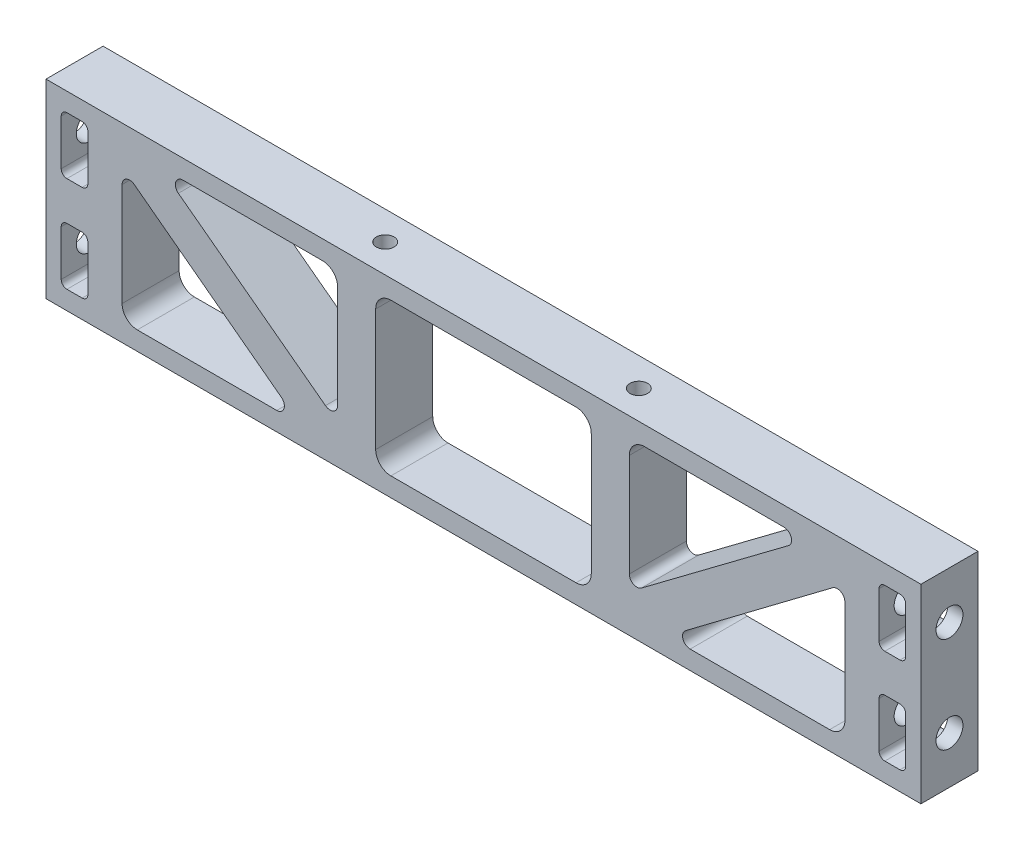
SolidWorks part; units mm, degrees
material "PE High Density"
ref_plane "Front Plane" through (0, 0, 0) normal (0, 0, 1) x (1, 0, 0)
ref_plane "Top Plane" through (0, 0, 0) normal (0, 1, 0) x (1, 0, 0)
ref_plane "Right Plane" through (0, 0, 0) normal (1, 0, 0) x (0, 0, -1)
sketch "Sketch1" plane through (0, 0, 0) normal (0, 0, 1) x (1, 0, 0)
  line L0 (-24.3417, 15.875) -> (-24.3417, -15.875) construction
  line L1 (-73.025, 15.875) -> (73.025, 15.875)
  line L2 (-73.025, 15.875) -> (-73.025, -15.875)
  line L3 (-73.025, -15.875) -> (73.025, -15.875)
  line L4 (73.025, 15.875) -> (73.025, -15.875)
  line L5 (-73.025, 15.875) -> (73.025, -15.875) construction
  line L6 (-73.025, -15.875) -> (73.025, 15.875) construction
  line L7 (24.3417, 15.875) -> (24.3417, -15.875) construction
  line L9 (-69.85, -12.7) -> (-27.5167, 12.7) construction
  line L10 (-69.85, -12.7) -> (-69.85, 12.7) construction
  line L11 (-64.3071, -11.2256) -> (-29.9209, 9.4061)
  line L12 (-73.025, -15.875) -> (-24.3417, -15.875)
  line L13 (-73.025, -15.875) -> (-73.025, 15.875)
  line L14 (-73.025, 15.875) -> (-24.3417, 15.875)
  line L15 (-24.3417, -15.875) -> (-24.3417, 15.875) construction
  line L16 (-69.85, 12.7) -> (-27.5167, 12.7) construction
  line L17 (-27.5167, -12.7) -> (-27.5167, 12.7) construction
  line L18 (-69.85, -12.7) -> (-27.5167, -12.7) construction
  line L19 (-67.4457, -9.4061) -> (-33.0595, 11.2256)
  line L20 (-69.0332, -14.0613) -> (-26.6999, 11.3387) construction
  line L21 (-69.85, -8.0448) -> (-69.85, 11.1125)
  line L22 (-70.6668, -11.3387) -> (-28.3334, 14.0613) construction
  line L23 (-68.2625, 12.7) -> (-33.4679, 12.7)
  line L24 (-63.8988, -12.7) -> (-29.1042, -12.7)
  line L25 (-27.5167, -11.1125) -> (-27.5167, 8.0448)
  line L26 (-15.6238, -11.2256) -> (18.7624, 9.4061)
  line L27 (-18.7624, -9.4061) -> (15.6238, 11.2256)
  line L28 (-21.1667, -8.0448) -> (-21.1667, 11.1125)
  line L29 (-19.5792, 12.7) -> (15.2154, 12.7)
  line L30 (-15.2154, -12.7) -> (19.5792, -12.7)
  line L31 (21.1667, -11.1125) -> (21.1667, 8.0448)
  line L32 (-21.1667, -12.7) -> (21.1667, 12.7) construction
  line L33 (-21.1667, -12.7) -> (-21.1667, 12.7) construction
  line L34 (-21.1667, 12.7) -> (21.1667, 12.7) construction
  line L35 (21.1667, -12.7) -> (21.1667, 12.7) construction
  line L36 (-21.1667, -12.7) -> (21.1667, -12.7) construction
  line L37 (33.0595, -11.2256) -> (67.4457, 9.4061)
  line L38 (29.9209, -9.4061) -> (64.3071, 11.2256)
  line L39 (27.5167, -8.0448) -> (27.5167, 11.1125)
  line L40 (29.1042, 12.7) -> (63.8988, 12.7)
  line L41 (33.4679, -12.7) -> (68.2625, -12.7)
  line L42 (69.85, -11.1125) -> (69.85, 8.0448)
  line L43 (27.5167, -12.7) -> (69.85, 12.7) construction
  line L44 (27.5167, -12.7) -> (27.5167, 12.7) construction
  line L45 (27.5167, 12.7) -> (69.85, 12.7) construction
  line L46 (69.85, -12.7) -> (69.85, 12.7) construction
  line L47 (27.5167, -12.7) -> (69.85, -12.7) construction
  line L59 (-64.3071, -11.2256) -> (-15.6238, -11.2256) construction
  line L60 (-69.85, 15.875) -> (-69.85, -15.875)
  arc A0 (-33.4679, 12.7) -> (-33.0595, 11.2256) centre (-33.4679, 11.9062) cw
  arc A1 (-69.85, -8.0448) -> (-67.4457, -9.4061) centre (-68.2625, -8.0448) ccw
  arc A2 (-69.85, 11.1125) -> (-68.2625, 12.7) centre (-68.2625, 11.1125) cw
  arc A3 (-27.5167, 8.0448) -> (-29.9209, 9.4061) centre (-29.1042, 8.0448) ccw
  arc A4 (-63.8988, -12.7) -> (-64.3071, -11.2256) centre (-63.8988, -11.9062) cw
  arc A5 (-27.5167, -11.1125) -> (-29.1042, -12.7) centre (-29.1042, -11.1125) cw
  arc A6 (15.2154, 12.7) -> (15.6238, 11.2256) centre (15.2154, 11.9062) cw
  arc A7 (-21.1667, -8.0448) -> (-18.7624, -9.4061) centre (-19.5792, -8.0448) ccw
  arc A8 (-21.1667, 11.1125) -> (-19.5792, 12.7) centre (-19.5792, 11.1125) cw
  arc A9 (21.1667, 8.0448) -> (18.7624, 9.4061) centre (19.5792, 8.0448) ccw
  arc A10 (-15.2154, -12.7) -> (-15.6238, -11.2256) centre (-15.2154, -11.9062) cw
  arc A11 (21.1667, -11.1125) -> (19.5792, -12.7) centre (19.5792, -11.1125) cw
  arc A12 (63.8988, 12.7) -> (64.3071, 11.2256) centre (63.8988, 11.9062) cw
  arc A13 (27.5167, -8.0448) -> (29.9209, -9.4061) centre (29.1042, -8.0448) ccw
  arc A14 (27.5167, 11.1125) -> (29.1042, 12.7) centre (29.1042, 11.1125) cw
  arc A15 (69.85, 8.0448) -> (67.4457, 9.4061) centre (68.2625, 8.0448) ccw
  arc A16 (33.4679, -12.7) -> (33.0595, -11.2256) centre (33.4679, -11.9062) cw
  arc A17 (69.85, -11.1125) -> (68.2625, -12.7) centre (68.2625, -11.1125) cw
  point P0 (0, 0)
  point P26 (-30.6022, 12.7)
  point P29 (-69.85, -10.8487)
  point P35 (-27.5167, 10.8487)
  point P38 (-66.7645, -12.7)
  dimension "D7" = 0.7937
  dimension "D8" = 1.5875
  dimension "D9" = 1.5875
  dimension "D10" = 1.5875
  dimension "D11" = 0.7937
  dimension "D12" = 1.5875
  dimension "D1" = 31.75
  dimension "CrossBraceLength" = 146.05
  dimension "D4" = 48.6833
  dimension "D14" = 48.6833
  dimension "D6" = 3.175
  dimension "D2" = 1.5875
  dimension "D5" = 1.5875
  dimension "D3" = 3
  dimension "D13" = 3
extrude "Boss-Extrude1" [suppressed] add sketch "Sketch1" along normal blind 9.525
sketch "Sketch2" plane through (0, 0, 0) normal (0, 0, 1) x (1, 0, 0)
  line L0 (-63.5, 15.875) -> (-63.5, -15.875) construction
  line L1 (-73.025, 15.875) -> (73.025, 15.875)
  line L2 (-73.025, 15.875) -> (-73.025, -15.875)
  line L3 (-73.025, -15.875) -> (73.025, -15.875)
  line L4 (73.025, 15.875) -> (73.025, -15.875)
  line L5 (-73.025, 15.875) -> (73.025, -15.875) construction
  line L6 (-73.025, -15.875) -> (73.025, 15.875) construction
  line L7 (0, 15.875) -> (0, -15.875) construction
  line L8 (-63.5, -15.875) -> (-63.5, 15.875) construction
  line L9 (63.5, 15.875) -> (63.5, -15.875) construction
  line L10 (-21.1667, 15.875) -> (-21.1667, -15.875) construction
  line L11 (-73.025, 0) -> (73.025, 0) construction
  line L12 (21.1667, 15.875) -> (21.1667, -15.875) construction
  line L14 (-63.5, -15.875) -> (-63.5, 15.875) construction
  line L15 (-63.5, 15.875) -> (-21.1667, 15.875)
  line L19 (-63.5, 15.875) -> (-21.1667, -15.875) construction
  line L20 (-63.5, -15.875) -> (-21.1667, -15.875)
  line L21 (-21.1667, 15.875) -> (-63.5, 15.875)
  line L22 (-63.5, -15.875) -> (-21.1667, -15.875)
  line L23 (-63.5, -15.875) -> (-63.5, 15.875) construction
  line L27 (-63.5, 15.875) -> (-21.1667, -15.875) construction
  line L28 (-50.927, 10.414) -> (-26.3737, -8.001)
  line L29 (-60.325, -10.2225) -> (-60.325, 6.985)
  line L48 (-57.785, -12.7625) -> (-34.5017, -12.7625)
  line L61 (-69.5325, 12.7625) -> (-66.9925, 12.7625)
  line L62 (-70.485, 11.81) -> (-70.485, 4.19)
  line L63 (-69.5325, 3.2375) -> (-66.9925, 3.2375)
  line L64 (-66.04, 11.81) -> (-66.04, 4.19)
  line L65 (-70.485, 12.7625) -> (-66.04, 3.2375) construction
  line L66 (-70.485, 3.2375) -> (-66.04, 12.7625) construction
  line L67 (-68.2625, 15.875) -> (-68.2625, -15.875) construction
  line L68 (-68.2625, 3.2375) -> (-68.2625, 11.967) construction
  line L69 (-70.485, 8) -> (-66.04, 8) construction
  line L70 (-70.485, -8) -> (-66.04, -8) construction
  line L71 (-68.2625, -3.2375) -> (-68.2625, -11.967) construction
  line L72 (-70.485, -3.2375) -> (-66.04, -12.7625) construction
  line L73 (-70.485, -12.7625) -> (-66.04, -3.2375) construction
  line L74 (-66.04, -11.81) -> (-66.04, -4.19)
  line L75 (-69.5325, -3.2375) -> (-66.9925, -3.2375)
  line L76 (-70.485, -11.81) -> (-70.485, -4.19)
  line L77 (-69.5325, -12.7625) -> (-66.9925, -12.7625)
  line L78 (-58.2913, 7.9998) -> (-33.738, -10.4777)
  line L79 (70.485, -12.7) -> (66.04, -3.175) construction
  line L80 (70.485, -3.175) -> (66.04, -12.7) construction
  line L81 (68.2625, -3.175) -> (68.2625, -11.967) construction
  line L82 (70.485, -7.9375) -> (66.04, -7.9375) construction
  line L83 (70.485, 7.9375) -> (66.04, 7.9375) construction
  line L84 (68.2625, 3.175) -> (68.2625, 11.967) construction
  line L85 (68.2625, 15.875) -> (68.2625, -15.875) construction
  line L86 (70.485, 3.175) -> (66.04, 12.7) construction
  line L87 (70.485, 12.7) -> (66.04, 3.175) construction
  line L88 (69.5325, -12.7) -> (66.9925, -12.7)
  line L89 (70.485, -11.7475) -> (70.485, -4.1275)
  line L90 (69.5325, -3.175) -> (66.9925, -3.175)
  line L91 (66.04, -11.7475) -> (66.04, -4.1275)
  line L92 (66.04, 11.7475) -> (66.04, 4.1275)
  line L93 (69.5325, 3.175) -> (66.9925, 3.175)
  line L94 (70.485, 11.7475) -> (70.485, 4.1275)
  line L95 (69.5325, 12.7) -> (66.9925, 12.7)
  line L96 (73.025, 15.875) -> (73.025, -15.875)
  line L97 (-63.5, 15.875) -> (-24.3417, 15.875)
  line L99 (-60.325, -15.875) -> (-60.325, 15.875) construction
  line L102 (-24.3417, 10.16) -> (-24.3417, -6.985)
  line L104 (-50.165, 12.7) -> (-26.8817, 12.7)
  line L105 (24.3417, 10.16) -> (24.3417, -6.985)
  line L106 (-24.3417, 15.875) -> (-24.3417, -15.875) construction
  line L107 (50.165, 12.7) -> (26.8817, 12.7)
  line L108 (50.927, 10.414) -> (26.3737, -8.001)
  line L109 (57.785, -12.7625) -> (34.5017, -12.7625)
  line L110 (58.2913, 7.9998) -> (33.738, -10.4777)
  line L111 (60.325, -10.2225) -> (60.325, 6.985)
  line L112 (0, -15.875) -> (0, -12.7)
  line L114 (-15.4517, 12.7) -> (15.4517, 12.7)
  line L115 (-17.9917, 10.16) -> (-17.9917, -10.16)
  line L116 (-15.4517, -12.7) -> (15.4517, -12.7)
  line L117 (17.9917, 10.16) -> (17.9917, -10.16)
  line L118 (-17.9917, 12.7) -> (17.9917, -12.7) construction
  line L119 (-17.9917, -12.7) -> (17.9917, 12.7) construction
  arc A36 (-66.9925, 3.2375) -> (-66.04, 4.19) centre (-66.9925, 4.19) ccw
  arc A37 (-66.9925, 12.7625) -> (-66.04, 11.81) centre (-66.9925, 11.81) cw
  arc A38 (-69.5325, 3.2375) -> (-70.485, 4.19) centre (-69.5325, 4.19) cw
  arc A39 (-69.5325, 12.7625) -> (-70.485, 11.81) centre (-69.5325, 11.81) ccw
  arc A40 (-69.5325, -12.7625) -> (-70.485, -11.81) centre (-69.5325, -11.81) cw
  arc A41 (-69.5325, -3.2375) -> (-70.485, -4.19) centre (-69.5325, -4.19) ccw
  arc A42 (-66.9925, -12.7625) -> (-66.04, -11.81) centre (-66.9925, -11.81) ccw
  arc A43 (-66.9925, -3.2375) -> (-66.04, -4.19) centre (-66.9925, -4.19) cw
  arc A44 (66.9925, -3.175) -> (66.04, -4.1275) centre (66.9925, -4.1275) ccw
  arc A45 (66.9925, -12.7) -> (66.04, -11.7475) centre (66.9925, -11.7475) cw
  arc A46 (69.5325, -3.175) -> (70.485, -4.1275) centre (69.5325, -4.1275) cw
  arc A47 (69.5325, -12.7) -> (70.485, -11.7475) centre (69.5325, -11.7475) ccw
  arc A48 (69.5325, 12.7) -> (70.485, 11.7475) centre (69.5325, 11.7475) cw
  arc A49 (69.5325, 3.175) -> (70.485, 4.1275) centre (69.5325, 4.1275) ccw
  arc A50 (66.9925, 12.7) -> (66.04, 11.7475) centre (66.9925, 11.7475) ccw
  arc A51 (66.9925, 3.175) -> (66.04, 4.1275) centre (66.9925, 4.1275) cw
  arc A52 (-57.785, -12.7625) -> (-60.325, -10.2225) centre (-57.785, -10.2225) cw
  arc A53 (-60.325, 6.985) -> (-58.2913, 7.9998) centre (-59.055, 6.985) cw
  arc A54 (-34.5017, -12.7625) -> (-33.738, -10.4777) centre (-34.5017, -11.4925) ccw
  arc A55 (-26.8817, 12.7) -> (-24.3417, 10.16) centre (-26.8817, 10.16) cw
  arc A56 (-26.3737, -8.001) -> (-24.3417, -6.985) centre (-25.6117, -6.985) ccw
  arc A57 (-50.927, 10.414) -> (-50.165, 12.7) centre (-50.165, 11.43) cw
  arc A58 (26.3737, -8.001) -> (24.3417, -6.985) centre (25.6117, -6.985) cw
  arc A59 (26.8817, 12.7) -> (24.3417, 10.16) centre (26.8817, 10.16) ccw
  arc A60 (50.927, 10.414) -> (50.165, 12.7) centre (50.165, 11.43) ccw
  arc A61 (57.785, -12.7625) -> (60.325, -10.2225) centre (57.785, -10.2225) ccw
  arc A62 (34.5017, -12.7625) -> (33.738, -10.4777) centre (34.5017, -11.4925) cw
  arc A63 (60.325, 6.985) -> (58.2913, 7.9998) centre (59.055, 6.985) ccw
  arc A64 (-15.4517, -12.7) -> (-17.9917, -10.16) centre (-15.4517, -10.16) cw
  arc A65 (-17.9917, 10.16) -> (-15.4517, 12.7) centre (-15.4517, 10.16) cw
  arc A66 (17.9917, 10.16) -> (15.4517, 12.7) centre (15.4517, 10.16) ccw
  arc A67 (17.9917, -10.16) -> (15.4517, -12.7) centre (15.4517, -10.16) cw
  point P16 (-68.2625, 8)
  point P18 (-65.405, 13.335)
  point P19 (-23.0717, -18.415)
  point P24 (-63.5, 12.7)
  point P26 (-24.3417, 12.7)
  point P34 (-61.595, 18.415)
  point P36 (-19.2617, -13.335)
  point P65 (0, 0)
  point P124 (-68.2625, -8)
  point P168 (68.2625, -7.9375)
  point P169 (68.2625, 7.9375)
  dimension "D19" = 0.9525
  dimension "D20" = 0.9525
  dimension "D21" = 0.9525
  dimension "D22" = 0.9525
  dimension "D6" = 2.54
  dimension "D8" = 1.27
  dimension "D9" = 1.27
  dimension "D11" = 2.54
  dimension "D12" = 1.27
  dimension "D13" = 1.27
  dimension "D16" = 2.54
  dimension "D1" = 146.05
  dimension "D2" = 31.75
  dimension "D3" = 9.525
  dimension "D17" = 4.445
  dimension "D18" = 9.525
  dimension "D23" = 4.7625
  dimension "D4" = 42.3333
  dimension "D5" = 42.3333
  dimension "D14" = 3.175
  dimension "D15" = 35.9833
  dimension "D24" = 8
  dimension "D7" = 3.175
  dimension "D10" = 3.175
extrude "Boss-Extrude2" add sketch "Sketch2" along normal blind 9.525 contours L4 L1 L2 L3 region at (-68.2625, 14.3804, 0)
sketch "Sketch3" plane through (-73.025, 0, 0) normal (-1, 0, 0) x (0, 0, 1)
  line L0 (9.525, 15.875) -> (0, 15.875) construction
  line L1 (0, 0) -> (9.525, 0) construction
  line L2 (9.525, 15.875) -> (9.525, -15.875) construction
  line L3 (4.7625, -15.875) -> (4.7625, 15.875) construction
  line L4 (9.525, -15.875) -> (0, -15.875) construction
  circle A0 centre (4.7625, 8) radius 2.2479
  dimension "D2" = 4.4958
  dimension "D1" = 8
extrude "Cut-Extrude1" cut sketch "Sketch3" against normal blind 11.1125
mirror "Mirror1" about plane through (0, 0, 0) normal (1, 0, 0) of "Cut-Extrude1" second plane through (0, 0, 0) second plane normal (0, 1, 0)
sketch "Sketch4" plane through (0, 15.875, 0) normal (0, 1, 0) x (1, 0, 0)
  line L2 (17.9917, -9.525) -> (17.9917, 0) construction
  line L3 (17.9917, -9.525) -> (17.9917, 0) construction
  line L4 (73.025, 0) -> (-73.025, 0)
  line L5 (-73.025, 0) -> (-73.025, -9.525)
  line L6 (-73.025, -9.525) -> (73.025, -9.525)
  line L7 (73.025, -9.525) -> (73.025, 0)
  line L8 (73.025, 0) -> (-73.025, 0) construction
  line L9 (-73.025, 0) -> (-73.025, -9.525) construction
  line L10 (-73.025, -9.525) -> (73.025, -9.525) construction
  line L11 (73.025, -9.525) -> (73.025, 0) construction
  line L12 (-17.9917, -9.525) -> (-17.9917, 0) construction
  line L13 (-17.9917, -9.525) -> (-17.9917, 0) construction
  line L14 (-24.3417, -9.525) -> (-24.3417, 0) construction
  line L15 (-24.3417, -9.525) -> (-24.3417, 0) construction
  line L16 (24.3417, -9.525) -> (24.3417, 0) construction
  line L17 (24.3417, -9.525) -> (24.3417, 0) construction
  line L18 (24.3417, -9.525) -> (17.9917, 0) construction
  line L19 (17.9917, -9.525) -> (24.3417, 0) construction
  circle A0 centre (21.1667, -4.7625) radius 1.4732
  dimension "D2" = 2.9464
  dimension "D1" = 0
extrude "Cut-Extrude2" cut sketch "Sketch4" against normal blind 12.7 contours A0
mirror "Mirror2" about plane through (0, 0, 0) normal (0, 1, 0) of "Cut-Extrude2" second plane through (0, 0, 0) second plane normal (1, 0, 0)
equation "\"Plate Width\" = 3.5in"
equation "\"Plate Thickness\" = 0.375in"
equation "\"Num holes\" = 4"
equation "\"Plate Height\" = 1.25in"
equation "\"Top Plate Width\" = 4.5in"
equation "\"Plate Clearance Hole Diameter\" = 0.125in"
equation "\"Plate Tap Hole Diameter\" = 0.116in"
equation "\"Bottom Plate Length\" = 6.5in"
equation "\"CrossBraceLength@Sketch1\" = \"Bottom Plate Length\" - 2 * \"Plate Thickness\""
equation "\"D1@Sketch1\"=\"Plate Height\""
equation "\"num_triangle_holes\"= 3"
equation "\"D3@Sketch1\"=\"num_triangle_holes\""
equation "\"D4@Sketch1\"=( \"Bottom Plate Length\" - 2 * \"Plate Thickness\" ) / \"num_triangle_holes\""
equation "\"BorderThickness\"= 0.125"
equation "\"D6@Sketch1\"=\"BorderThickness\""
equation "\"D2@Sketch1\"=\"BorderThickness\"/2"
equation "\"D9@Sketch1\"=\"BorderThickness\"/2"
equation "\"D8@Sketch1\"=\"BorderThickness\"/2"
equation "\"D7@Sketch1\"=\"BorderThickness\"/4"
equation "\"D10@Sketch1\"=\"BorderThickness\"/2"
equation "\"D11@Sketch1\"=\"BorderThickness\"/4"
equation "\"D12@Sketch1\"=\"BorderThickness\"/2"
equation "\"D13@Sketch1\"=\"num_triangle_holes\""
equation "\"D14@Sketch1\"=( \"Bottom Plate Length\" - 2 * \"Plate Thickness\" ) / \"num_triangle_holes\""
equation "\"D1@Boss-Extrude1\"=\"Plate Thickness\""
equation "\"D1@Sketch2\"=\"Bottom Plate Length\" - 2 * \"Plate Thickness\""
equation "\"D2@Sketch2\"=\"Plate Height\""
equation "\"wall_thickness\"= 0.375"
equation "\"D3@Sketch2\"=\"wall_thickness\""
equation "\"D1@Boss-Extrude2\"=\"Plate Thickness\""
equation "\"D23@Sketch2\"=\"wall_thickness\"/2"
equation "\"Number Eight Clearance Size\" = 0.177in"
equation "\"D2@Sketch3\"=\"Number Eight Clearance Size\""
equation "\"D1@Cut-Extrude1\"=(0.75 - \"Plate Thickness\") + 0.0625"
equation "\"D4@Sketch2\"=( ( \"Bottom Plate Length\" - 2 * \"Plate Thickness\" ) - \"Plate Thickness\" * 2 ) /3"
equation "\"D5@Sketch2\"=( ( \"Bottom Plate Length\" - 2 * \"Plate Thickness\" ) - \"Plate Thickness\" * 2 ) /3"
equation "\"D14@Sketch2\"=\"BorderThickness\""
equation "\"D15@Sketch2\"=( ( ( \"Bottom Plate Length\" - 2 * \"Plate Thickness\" ) - \"Plate Thickness\" * 2 ) /3 ) - \"BorderThickness\"*2"
